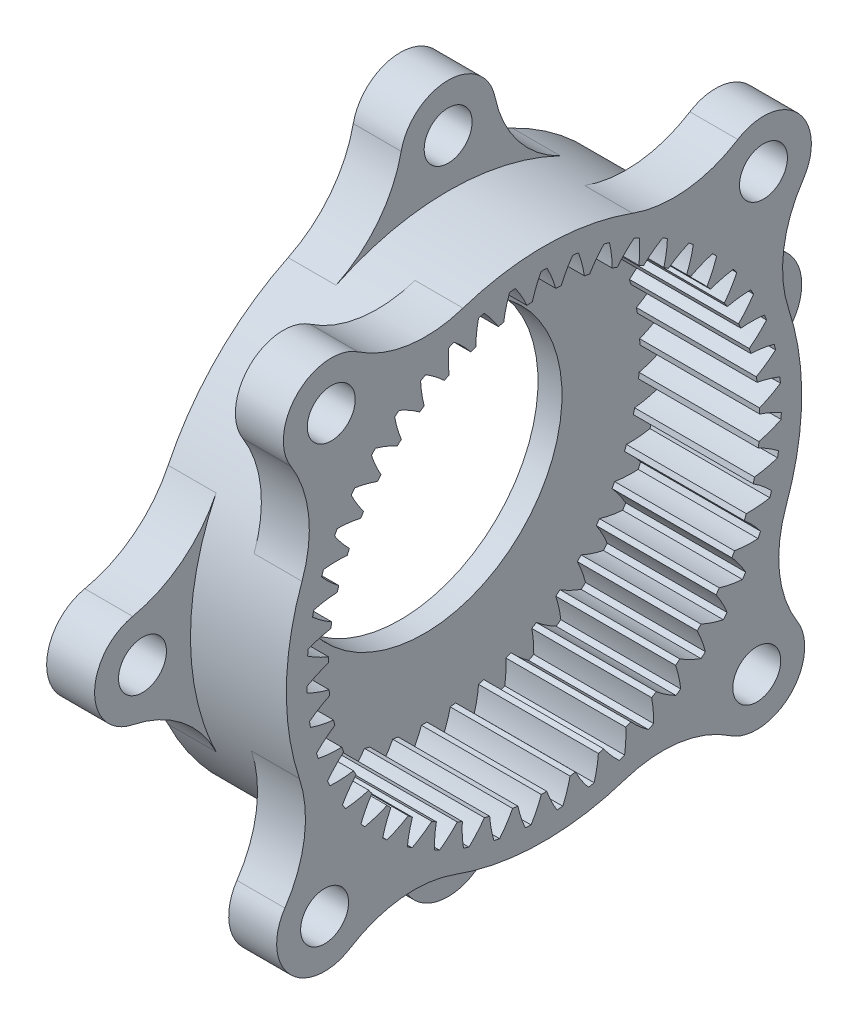
SolidWorks part; units mm, degrees
ref_plane "Plane1" through (0, 0, 0) normal (0, 0, 1) x (1, 0, 0)
ref_plane "Plane2" through (0, 0, 0) normal (0, 1, 0) x (1, 0, 0)
ref_plane "Plane3" through (0, 0, 0) normal (1, 0, 0) x (0, 0, -1)
other "Configuration Table"
sketch "HoldingSke" plane through (0, 0, 0) normal (0, 1, 0) x (1, 0, 0)
  line L0 (0, 0) -> (0.8525, -0.9142)
  line L1 (-15, 0) -> (100, 0) construction
  line L2 (0, 0) -> (-2.1039, 2.3779)
  line L3 (0, 0) -> (-11.863, 4.5341)
  line L4 (0, 0) -> (5.8897, 6.316)
  line L5 (0, 0) -> (-23.7986, -8.8762)
  line L6 (0, 0) -> (-10.5278, -7.1032)
  line L7 (-2.1039, 2.3779) -> (3.3635, 27.1825)
  line L8 (-76.2, 3.1779) -> (-54.61, 3.1779)
  line L9 (-71.009, 38.7566) -> (-53.1078, 45.2721)
  line L10 (-76.2, 71.12) -> (104.1128, 71.12)
  line L11 (0, 0) -> (-12, 0)
  line L12 (-76.2, 101.6) -> (-76.17, 101.6)
  line L13 (24.9733, 27.94) -> (52.9518, 28.4284)
  line L14 (24.9733, 27.94) -> (24.9743, 27.94)
  line L15 (24.9733, 27.94) -> (100.4006, 29.5858)
  circle A0 centre (0, 0) radius 21.5
  circle A1 centre (0, 0) radius 12.7
  circle A2 centre (0, 0) radius 12.7
  dimension "MHD" = 25.4
  dimension "Hub_dia" = 25.4
  dimension "Diameter" = 43
  dimension "Num_teeth" = 47
  dimension "Pitch" = 1.25
  dimension "Overall_len" = 25.4
  dimension "Show_teeth" = 47
  dimension "Thickness" = 12.7
  dimension "OAL" = 25.4001
  dimension "T_dim" = 21.59
  dimension "Ap" = 20
  dimension "H" = 19.05
  dimension "Pitch_radius" = 180.3128
  dimension "Width" = 12
  dimension "Backlash" = 0.03
  dimension "Addendum_fac" = 1
  dimension "Dedendum_fac" = 1.25
  dimension "Clearance_fac" = 0.25
  dimension "Dedendum_add" = 0.001
  dimension "Module" = 0.8
sketch "BasProSke" plane through (0, 0, 0) normal (0, 1, 0) x (1, 0, 0)
  line L0 (-10, 0) -> (60, 0) construction
  line L1 (0, 18) -> (0, 21.5)
  line L2 (0, 18) -> (12, 18)
  line L3 (12, 18) -> (12, 21.5)
  line L4 (12, 21.5) -> (0, 21.5)
  dimension "Diameter" = 43
  dimension "Thickness" = 12
  dimension "Inside_diameter" = 36
revolve "Base-Revolve" add sketch "BasProSke" angle 360 about L0
sketch "TooCutSke" plane through (0, 0, 0) normal (1, 0, 0) x (0, 0, -1)
  line L3 (0.7032, 18.7868) -> (0.7032, 53.6633) construction
  line L4 (0, 0) -> (0, 59.563) construction
  line L5 (0, 0) -> (-4.5638, 68.1749) construction
  line L6 (-8.0637, 15.3954) -> (36.6963, 18.3917) construction
  circle A0 centre (0, 0) radius 18.8 construction
  circle A1 centre (0, 0) radius 19.801 construction
  circle A2 centre (0, 0) radius 15.8996 construction
  circle A3 centre (0, 0) radius 17.9746 construction
  arc A4 (0.9832, 17.9477) -> (0.2408, 19.7995) centre (-8.0637, 15.3954) ccw
  arc A5 (0.9832, 17.9477) -> (-0.9832, 17.9477) centre (0, 0) ccw
  arc A6 (0.2408, 19.7995) -> (-0.2408, 19.7995) centre (0, 0) ccw
  arc A7 (-0.2408, 19.7995) -> (-0.9832, 17.9477) centre (8.0637, 15.3954) ccw
  dimension "Pitch_dia" = 37.6
  dimension "Base_dia" = 31.7992
  dimension "Root_dia" = 39.602
  dimension "Overcut_dia" = 35.9492
  dimension "Flank_rad" = 9.4
  dimension "Half_ang" = 3.83
  dimension "Half_CT" = 0.7032
extrude "ToothCut" cut sketch "TooCutSke" along normal through all
fillet "Breaks" [suppressed] radius 0.08
fillet "RootFillets" [suppressed] radius 0.201
pattern_circular "TeethCuts" count 47 every 7.66 about axis through (-10, 0, 0) along (1, 0, 0) of "RootFillets", "Breaks", "ToothCut"
sketch "Sketch1" plane through (0, 0, 0) normal (-1, 0, 0) x (0, 0, 1)
  circle A0 centre (0, 0) radius 21.5
  dimension "D1" = 43
extrude "Boss-Extrude1" add sketch "Sketch1" against normal blind 2
sketch "Sketch2" plane through (0, 0, 0) normal (-1, 0, 0) x (0, 0, 1)
  circle A0 centre (0, 0) radius 11.5
  dimension "D1" = 23
extrude "Cut-Extrude1" cut sketch "Sketch2" against normal through all
sketch "Sketch3" plane through (0, 0, 0) normal (-1, 0, 0) x (0, 0, 1)
  line L0 (-25.5, 4) -> (-20.0965, 4)
  line L1 (-20.0965, 4) -> (-20.0965, -4)
  line L2 (-20.0965, -4) -> (-25.5, -4)
  line L3 (4, 25.5) -> (4, 20.0965)
  line L4 (-4, 20.0965) -> (-4, 25.5)
  line L5 (4, 20.0965) -> (-4, 20.0965)
  line L6 (25.5, -4) -> (20.0965, -4)
  line L7 (20.0965, 4) -> (25.5, 4)
  line L8 (20.0965, -4) -> (20.0965, 4)
  line L9 (-4, -25.5) -> (-4, -20.0965)
  line L10 (4, -20.0965) -> (4, -25.5)
  line L11 (-4, -20.0965) -> (4, -20.0965)
  circle A0 centre (0, 0) radius 25.5 construction
  circle A1 centre (-25.5, 0) radius 2
  arc A3 (-25.5, 4) -> (-25.5, -4) centre (-25.5, 0) ccw
  arc A4 (4, 25.5) -> (-4, 25.5) centre (0, 25.5) ccw
  circle A5 centre (0, 25.5) radius 2
  arc A6 (25.5, -4) -> (25.5, 4) centre (25.5, 0) ccw
  circle A7 centre (25.5, 0) radius 2
  arc A8 (-4, -25.5) -> (4, -25.5) centre (0, -25.5) ccw
  circle A9 centre (0, -25.5) radius 2
  circle A10 centre (0, 0) radius 21.5 construction
  point P40 (0, 0)
  dimension "D1" = 4
  dimension "D2" = 2
  dimension "D3" = 4
extrude "Boss-Extrude3" add sketch "Sketch3" against normal blind 4
sketch "Sketch4" plane through (12, 0, 0) normal (1, 0, 0) x (0, 0, -1)
  line L1 (-7.8899, -20) -> (7.8899, -20)
  line L2 (-20, -7.8899) -> (-20, 7.8899)
  line L3 (-7.8899, 20) -> (7.8899, 20)
  line L4 (20, -7.8899) -> (20, 7.8899)
  arc A0 (-20, 7.8899) -> (-20, -7.8899) centre (0, 0) ccw
  arc A1 (7.8899, 20) -> (-7.8899, 20) centre (0, 0) ccw
  arc A2 (20, -7.8899) -> (20, 7.8899) centre (0, 0) ccw
  arc A3 (-7.8899, -20) -> (7.8899, -20) centre (0, 0) ccw
extrude "Cut-Extrude2" [suppressed] cut sketch "Sketch4" against normal up to surface (8 mm away)
fillet "Fillet1" radius 10 8 edges at (2, -21.1246, 4) (2, -4, 21.1246) (2, 4, 21.1246) (2, 21.1246, 4) (2, 21.1246, -4) (2, 4, -21.1246) (2, -4, -21.1246) (2, -21.1246, -4)
sketch "Sketch6" plane through (12, 0, 0) normal (1, 0, 0) x (0, 0, -1)
  line L0 (-7.3194, 0) -> (8.4347, 0) construction
  line L1 (0.5577, 0) -> (-19.5488, 20.1064) construction
  line L4 (-20.5787, 15.4795) -> (-16.7267, 11.6275)
  line L5 (-14.9218, 21.1363) -> (-11.0698, 17.2844)
  line L6 (-16.7267, 11.6275) -> (-11.0698, 17.2844)
  line L7 (11.6275, 16.7267) -> (17.2844, 11.0698)
  line L8 (15.4795, 20.5787) -> (11.6275, 16.7267)
  line L9 (21.1363, 14.9218) -> (17.2844, 11.0698)
  line L10 (16.7267, -11.6275) -> (11.0698, -17.2844)
  line L11 (20.5787, -15.4795) -> (16.7267, -11.6275)
  line L12 (14.9218, -21.1363) -> (11.0698, -17.2844)
  line L13 (-11.6275, -16.7267) -> (-17.2844, -11.0698)
  line L14 (-15.4795, -20.5787) -> (-11.6275, -16.7267)
  line L15 (-21.1363, -14.9218) -> (-17.2844, -11.0698)
  circle A0 centre (-17.7502, 18.3079) radius 2
  arc A2 (-19.09, 16.823) -> (-16.2653, 19.6477) centre (0.5577, 0) ccw construction
  arc A4 (-14.9218, 21.1363) -> (-20.5787, 15.4795) centre (-17.7502, 18.3079) ccw
  arc A5 (21.1363, 14.9218) -> (15.4795, 20.5787) centre (18.3079, 17.7502) ccw
  circle A6 centre (18.3079, 17.7502) radius 2
  arc A7 (14.9218, -21.1363) -> (20.5787, -15.4795) centre (17.7502, -18.3079) ccw
  circle A8 centre (17.7502, -18.3079) radius 2
  arc A9 (-21.1363, -14.9218) -> (-15.4795, -20.5787) centre (-18.3079, -17.7502) ccw
  circle A10 centre (-18.3079, -17.7502) radius 2
  circle A11 centre (0, 0) radius 21.5 construction
  point P37 (0, 0)
  dimension "D2" = 4
  dimension "D3" = 2
  dimension "D1" = 45
  dimension "D4" = 4
extrude "Boss-Extrude4" add sketch "Sketch6" against normal blind 4
fillet "Fillet2" radius 10 8 edges at (10, -11.7746, 17.9891) (10, -17.5371, 12.4379) (10, -17.9891, -11.7746) (10, -12.4379, -17.5371) (10, 11.7746, -17.9891) (10, 17.5371, -12.4379) (10, 17.9891, 11.7746) (10, 12.4379, 17.5371)
sketch "Sketch8" plane through (0, 0, 0) normal (-1, 0, 0) x (0, 0, 1)
  line L1 (-14.1421, 14.1421) -> (-15.2028, 15.2028) construction
  line L3 (8.5632, -19.7211) -> (19.7211, -8.5632)
  line L4 (-8.5632, -19.7211) -> (-19.7211, -8.5632)
  line L5 (-19.7211, 8.5632) -> (-8.5632, 19.7211)
  line L6 (19.7211, 8.5632) -> (8.5632, 19.7211)
  arc A0 (-8.5632, 19.7211) -> (-19.7211, 8.5632) centre (0, 0) ccw
  arc A1 (-19.7211, -8.5632) -> (-8.5632, -19.7211) centre (0, 0) ccw
  arc A2 (8.5632, -19.7211) -> (19.7211, -8.5632) centre (0, 0) ccw
  arc A3 (19.7211, 8.5632) -> (8.5632, 19.7211) centre (0, 0) ccw
extrude "Cut-Extrude3" [suppressed] cut sketch "Sketch8" against normal up to surface (8 mm away)
sketch "Sketch9" plane through (12, 0, 0) normal (1, 0, 0) x (0, 0, -1)
  circle A0 centre (0, 0) radius 29.5
  circle A1 centre (0, 0) radius 31.5
  dimension "D1" = 2
  dimension "D2" = 59
extrude "Cut-Extrude4" [suppressed] cut sketch "Sketch9" against normal through all
equation "' \"Module@HoldingSke\" = 6.35"
equation "' \"Num_teeth@HoldingSke\" = 24"
equation "' \"Ap@HoldingSke\" =  14.5"
equation "' \"Ap@HoldingSke\" = 14.5"
equation "' \"Width@HoldingSke\" = 12"
equation "' \"Diameter@HoldingSke\" = 8 * 25.4"
equation "' \"Show_teeth@HoldingSke\" = 100"
equation "' \"Backlash@HoldingSke\" = 0.009 * 25.4"
equation "' \"Addendum_fac@HoldingSke\" = 1.0"
equation "' \"Dedendum_fac@HoldingSke\" = 1.25"
equation "' \"Dedendum_add@HoldingSke\" = 0.00005 * 25.4"
equation "' \"Clearance_fac@HoldingSke\" = 0.25"
equation "\"Pitch@HoldingSke\" = 1 / \"Module@HoldingSke\" "
equation "\"Overcut_dia@TooCutSke\" = (\"Num_teeth@HoldingSke\" - 2 * \"Addendum_fac@HoldingSke\") / \"Pitch@HoldingSke\" - 0.002 * 25.4"
equation "\"Pitch_dia@TooCutSke\" = \"Num_teeth@HoldingSke\" / \"Pitch@HoldingSke\""
equation "\"Base_dia@TooCutSke\" = \"Num_teeth@HoldingSke\" / \"Pitch@HoldingSke\" * cos((\"Ap@HoldingSke\"  * 3.14159265 / 180)) * 0.90"
equation "\"Root_dia@TooCutSke\" = \"Num_teeth@HoldingSke\"  / \"Pitch@HoldingSke\" + 2 *  \"Dedendum_fac@HoldingSke\"/ \"Pitch@HoldingSke\" + \"Dedendum_add@HoldingSke\" * 2"
equation "\"Half_ang@TooCutSke\" = 180 / \"Num_teeth@HoldingSke\""
equation "\"Half_CT@TooCutSke\" = \"Num_teeth@HoldingSke\" / \"Pitch@HoldingSke\" * sin((3.14159265 / 2 / \"Num_teeth@HoldingSke\")) / 2 + 10 * \"Backlash@HoldingSke\" / 4"
equation "\"Flank_rad@TooCutSke\" = \"Num_teeth@HoldingSke\" / \"Pitch@HoldingSke\" / 4"
equation "\"Radius@RootFillets\"= \"Clearance_fac@HoldingSke\" / \"Pitch@HoldingSke\" + \"Dedendum_add@HoldingSke\""
equation "\"Break_rad@Breaks\" = 0.02 / \"Pitch@HoldingSke\" * 5"
equation "\"Num_teeth@TeethCuts\" = int( \"Show_teeth@HoldingSke\" ) + 1"
equation "\"Num_teeth@TeethCuts\" = ((sgn( \"Num_teeth@TeethCuts\" - \"Num_teeth@HoldingSke\" )-1)*( \"Num_teeth@TeethCuts\" - \"Num_teeth@HoldingSke\" ))/-2+ \"Num_teeth@HoldingSke\""
equation "\"Num_teeth@TeethCuts\" = ((sgn( \"Num_teeth@TeethCuts\" - 2.0)+1)*( \"Num_teeth@TeethCuts\" - 2.0))/2 +2.0"
equation "\"Angle@TeethCuts\" = 360.0 / \"Num_teeth@HoldingSke\""
equation "\"Diameter@BasProSke\" = \"Num_teeth@HoldingSke\"  / \"Pitch@HoldingSke\" + 2 *  \"Dedendum_fac@HoldingSke\"/ \"Pitch@HoldingSke\" + \"Dedendum_add@HoldingSke\" * 2 + 0.002 * 25.4"
equation "\"Diameter@BasProSke\" = ((sgn( \"Diameter@BasProSke\"  - \"Diameter@HoldingSke\" )+1)*( \"Diameter@BasProSke\"  - \"Diameter@HoldingSke\" ))/2 + \"Diameter@HoldingSke\""
equation "\"Inside_diameter@BasProSke\" =  (\"Num_teeth@HoldingSke\" - 2 * \"Addendum_fac@HoldingSke\") / \"Pitch@HoldingSke\" "
equation "\"Thickness@BasProSke\"  = \"Width@HoldingSke\""
